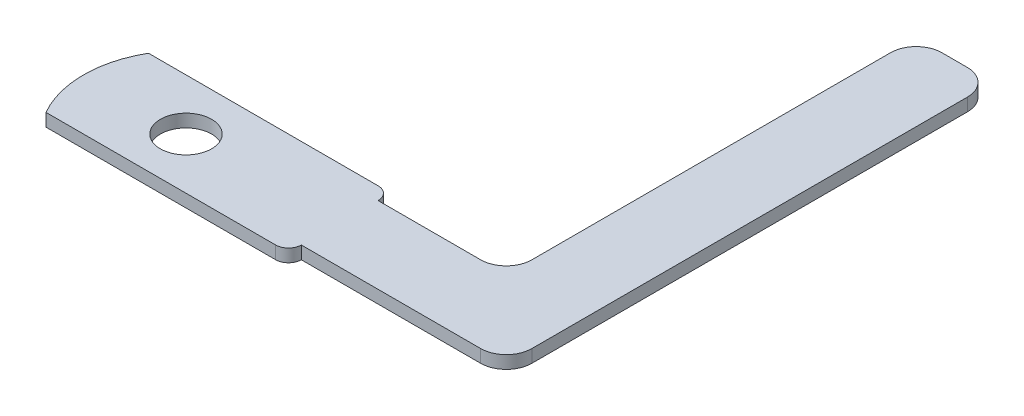
SolidWorks part; units mm, degrees
ref_plane "Front Plane" through (0, 0, 0) normal (0, 0, 1) x (1, 0, 0)
ref_plane "Top Plane" through (0, 0, 0) normal (0, 1, 0) x (1, 0, 0)
ref_plane "Right Plane" through (0, 0, 0) normal (1, 0, 0) x (0, 0, -1)
sketch "Sketch1" plane through (0, 0, 0) normal (0, 1, 0) x (1, 0, 0)
  line L0 (0, 6.35) -> (-19.05, 6.35) construction
  line L1 (0, 0) -> (-19.05, 0)
  line L2 (0, 0) -> (0, 12.7)
  line L3 (0, 12.7) -> (-19.05, 12.7)
  line L4 (-19.05, 0) -> (-19.05, 12.7) construction
  line L5 (0, 12.7) -> (12.7, 12.7)
  line L6 (12.7, 12.7) -> (12.7, 11.1125)
  line L7 (12.7, 11.1125) -> (28.575, 11.1125)
  line L8 (38.1, 11.1125) -> (38.1, 1.5875)
  line L9 (38.1, 1.5875) -> (12.7, 1.5875)
  line L10 (12.7, 1.5875) -> (12.7, 0)
  line L11 (12.7, 0) -> (0, 0)
  line L12 (38.1, 11.1125) -> (38.1, 61.9125)
  line L13 (38.1, 61.9125) -> (28.575, 61.9125)
  line L14 (28.575, 61.9125) -> (28.575, 11.1125)
  line L15 (28.575, 11.1125) -> (38.1, 11.1125) construction
  circle A0 centre (-6.35, 6.35) radius 3.175
  arc A1 (-17.3485, 12.7) -> (-17.3485, 0) centre (-6.35, 6.35) ccw
  dimension "D4" = 6.35
  dimension "D1" = 12.7
  dimension "D2" = 19.05
  dimension "D3" = 6.35
  dimension "D5" = 12.7
  dimension "D6" = 25.4
  dimension "D7" = 9.525
  dimension "D8" = 50.8
extrude "Boss-Extrude1" add sketch "Sketch1" along normal blind 1.5875 contours L2 L0 A0 L4 L1 | L0 L2 L3 L4 A0 | L11 L10 L9 L8 L6 L5 L2 region at (-9.7091, 0, -6.35) region at (0.727, 0, -6.35)
fillet "Fillet1" radius 3.175 4 edges at (38.1, 0.7937, -61.9125) (28.575, 0.7937, -61.9125) (28.575, 0.7937, -11.1125) (38.1, 0.7937, -1.5875)
fillet "Fillet2" radius 1.5875 2 edges at (12.7, 0.7937, 0) (12.7, 0.7937, -12.7)
